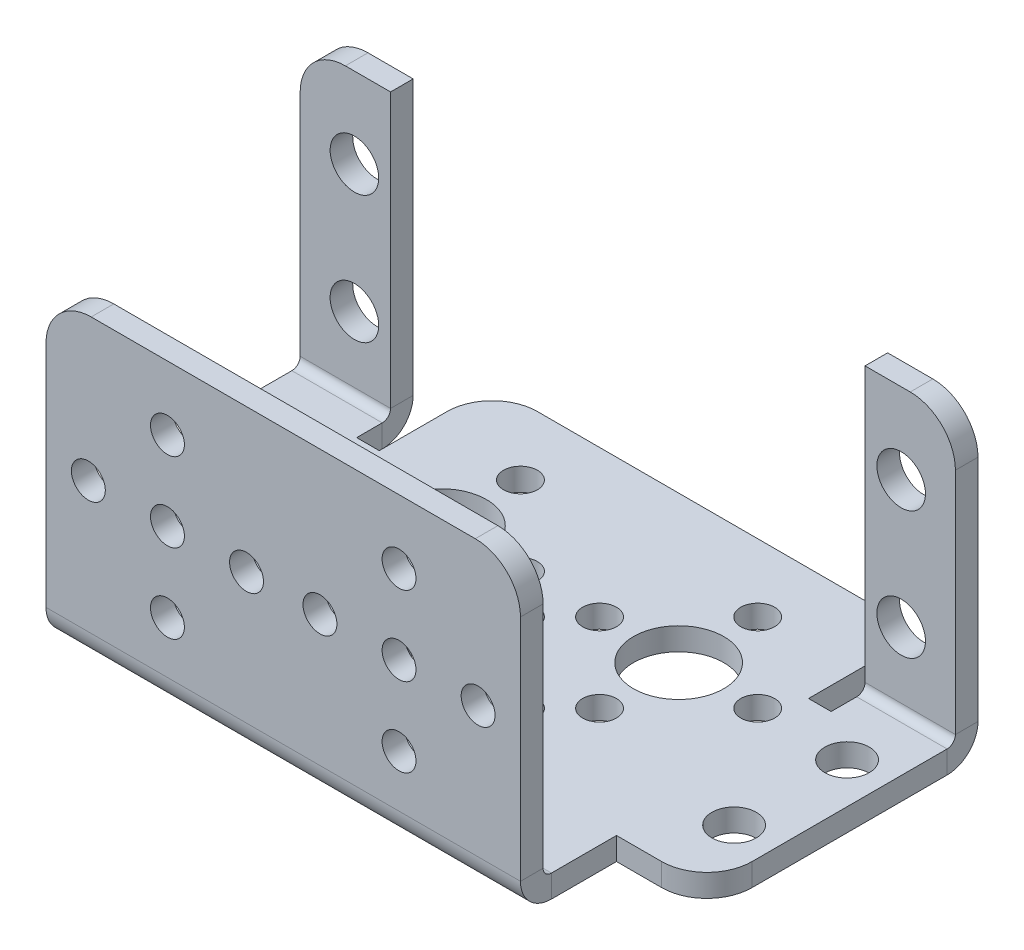
SolidWorks part; units mm, degrees
note: The reader was unsure of these and kept them because the rebuilt part matched: flange length of "Edge-Flange1", "Edge-Flange2", "Edge-Flange3".
ref_plane "Front Plane" through (0, 0, 0) normal (0, 0, 1) x (1, 0, 0)
ref_plane "Top Plane" through (0, 0, 0) normal (0, 1, 0) x (1, 0, 0)
ref_plane "Right Plane" through (0, 0, 0) normal (1, 0, 0) x (0, 0, -1)
sketch "Sketch2" plane through (0, 0, 0) normal (0, 1, 0) x (1, 0, 0)
  line L0 (-21, 12.8159) -> (-29, 12.8159)
  line L1 (-29, 12.8159) -> (-29, -9.1841)
  line L2 (-29, -9.1841) -> (-21, -9.1841)
  line L3 (-21, -9.1841) -> (-21, -15.6841)
  line L4 (-21, -15.6841) -> (21, -15.6841)
  line L5 (21, -15.6841) -> (21, -9.1841)
  line L6 (21, -9.1841) -> (29, -9.1841)
  line L7 (29, -9.1841) -> (29, 12.8159)
  line L8 (29, 12.8159) -> (21, 12.8159)
  line L9 (21, 12.8159) -> (21, 9.8159)
  line L10 (21, 9.8159) -> (19, 9.8159)
  line L11 (19, 9.8159) -> (19, 19.8159)
  line L12 (19, 19.8159) -> (-19, 19.8159)
  line L13 (-19, 19.8159) -> (-19, 9.8159)
  line L14 (-19, 9.8159) -> (-21, 9.8159)
  line L15 (-21, 9.8159) -> (-21, 12.8159)
  line L16 (-25, -3.1841) -> (-25, 6.8159) construction
  line L17 (25.4097, 6.8159) -> (25.4097, -3.1841) construction
  line L18 (-25, 6.8159) -> (-25, 12.8159) construction
  line L19 (-25, -3.1841) -> (-25, -9.1841) construction
  line L21 (-10.5, 6.8159) -> (10.5, 6.8159) construction
  circle A0 centre (-25, -3.1841) radius 1.9668
  circle A1 centre (-25, 6.8159) radius 1.9668
  circle A2 centre (25.4097, 6.8159) radius 1.9668
  circle A3 centre (25.4097, -3.1841) radius 1.9668
  circle A4 centre (-10.5, 6.8159) radius 4
  circle A5 centre (10.5, 6.8159) radius 4
  circle A6 centre (0, -3.6841) radius 4
  circle A7 centre (-10.5, 6.8159) radius 7 construction
  circle A8 centre (10.5, 6.8159) radius 7 construction
  circle A9 centre (0, -3.6841) radius 7 construction
  circle A10 centre (-10.5, 13.8159) radius 1.5
  circle A11 centre (10.5, 13.8159) radius 1.5
  circle A12 centre (0, -10.6841) radius 1.5
  circle A13 centre (-3.5, 6.8159) radius 1.5
  circle A14 centre (-10.5, -0.1841) radius 1.5
  circle A15 centre (-17.5, 6.8159) radius 1.5
  circle A16 centre (17.5, 6.8159) radius 1.5
  circle A17 centre (10.5, -0.1841) radius 1.5
  circle A18 centre (3.5, 6.8159) radius 1.5
  circle A19 centre (-7, -3.6841) radius 1.5
  circle A20 centre (0, 3.3159) radius 1.5
  circle A21 centre (7, -3.6841) radius 1.5
  point P2 (0, -15.6841)
  point P17 (0, 19.8159)
  point P19 (-25, 12.8159)
  point P28 (25.4097, 1.8159)
  point P29 (-25, 1.8159)
  point P36 (0, 6.8159)
  point P48 (-20, 9.8159)
  point P57 (-10.5, 6.8159)
  point P64 (10.5, 6.8159)
  point P71 (0, -3.6841)
  dimension "D8" = 8
  dimension "D10" = 14
  dimension "D11" = 3
  dimension "D1" = 58
  dimension "D2" = 35.5
  dimension "D3" = 28.5
  dimension "D4" = 38
  dimension "D5" = 12.5
  dimension "D6" = 10
  dimension "D7" = 21
  dimension "D9" = 12
  dimension "D15" = 2
  dimension "D16" = 10
  dimension "D12" = 4
  dimension "D13" = 4
  dimension "D14" = 4
base flange "Base-Flange1" sketch "Sketch2" thickness 2 reverse thickness direction no parameters "D1"=0.7366
fillet "Fillet1" radius 4 4 edges at (-19, -1, -19.8159) (19, -1, -19.8159) (29, -1, 9.1841) (-29, -1, 9.1841)
edge flange "Edge-Flange1" sketch "Sketch9" flange angle 90 flange length 27 flange position material outside bend radius 0.7366 thickness 2 relief rectangular parameters "D6"=10
sketch "Sketch9" plane through (0, 0, -12.8159) normal (0, 0, -1) x (-1, 0, 0)
  line L2 (21, 0) -> (21, 25)
  line L3 (21, 25) -> (29, 25)
  line L4 (29, 25) -> (29, 0)
  line L7 (21, 0) -> (29, 0) construction
  line L8 (21, 0) -> (29, 0)
bend "EdgeBend1" bend radius 0.7366 bend angle 90 parameters "D5"=1
edge flange "Edge-Flange2" sketch "Sketch12" flange angle 90 flange length 27 flange position material outside bend radius 0.7366 thickness 2 relief rectangular parameters "D6"=10
sketch "Sketch12" plane through (0, 0, -12.8159) normal (0, 0, -1) x (-1, 0, 0)
  line L0 (-29, 0) -> (-21, 0) construction
  line L1 (-29, 0) -> (-21, 0)
  line L2 (-29, 0) -> (-29, 25)
  line L3 (-29, 25) -> (-21, 25)
  line L4 (-21, 25) -> (-21, 0)
bend "EdgeBend2" bend radius 0.7366 bend angle 90 parameters "D5"=2
edge flange "Edge-Flange3" sketch "Sketch15" flange angle 90 flange length 27 flange position material outside bend radius 0.7366 thickness 2 relief rectangular parameters "D6"=10
sketch "Sketch15" plane through (0, 0, 15.6841) normal (0, 0, 1) x (1, 0, 0)
  line L0 (-21, 0) -> (21, 0) construction
  line L1 (-21, 0) -> (21, 0)
  line L2 (-21, 0) -> (-21, 25)
  line L3 (-21, 25) -> (21, 25)
  line L4 (21, 25) -> (21, 0)
bend "EdgeBend3" bend radius 0.7366 bend angle 90 parameters "D5"=3
fillet "Fillet2" radius 4 2 edges at (29, 25, -13.8159) (-29, 25, -13.8159)
fillet "Fillet3" radius 4 2 edges at (21, 25, 16.6841) (-21, 25, 16.6841)
sketch "Sketch16" plane through (0, 0, 17.6841) normal (0, 0, 1) x (1, 0, 0)
  line L0 (-10.25, 12.331) -> (10.25, 12.331) construction
  line L1 (-24.2, 17.8706) -> (24.2, 17.8706) construction
  line L2 (-24.2, 17.8706) -> (-24.2, 6.5706) construction
  line L3 (-24.2, 6.5706) -> (24.2, 6.5706) construction
  line L4 (24.2, 17.8706) -> (24.2, 6.5706) construction
  circle A0 centre (-24.2, 17.8706) radius 2.15
  circle A1 centre (24.2, 17.8706) radius 2.15
  circle A2 centre (-24.2, 6.5706) radius 2.15
  circle A3 centre (24.2, 6.5706) radius 2.15
  circle A4 centre (-10.25, 12.331) radius 7 construction
  circle A5 centre (10.25, 12.331) radius 7 construction
  circle A6 centre (-10.25, 12.331) radius 1.5
  circle A7 centre (-10.25, 5.331) radius 1.5
  circle A9 centre (10.25, 12.331) radius 1.5
  circle A10 centre (10.25, 5.331) radius 1.5
  circle A11 centre (-17.25, 12.331) radius 1.5
  circle A12 centre (-10.25, 19.331) radius 1.5
  circle A13 centre (-3.25, 12.331) radius 1.5
  circle A14 centre (3.25, 12.331) radius 1.5
  circle A15 centre (10.25, 19.331) radius 1.5
  circle A16 centre (17.25, 12.331) radius 1.5
  point P12 (0, 6.5706)
  point P16 (0, 12.331)
  point P38 (-10.25, 12.331)
  point P44 (10.25, 12.331)
  dimension "D3" = 4.3
  dimension "D4" = 14
  dimension "D5" = 3
  dimension "D1" = 48.4
  dimension "D2" = 11.3
  dimension "D8" = 13.95
  dimension "D6" = 4
  dimension "D7" = 4
extrude "Cut-Extrude1" cut sketch "Sketch16" against normal through all normal cut yes
sketch "Bend-Lines1" [suppressed] plane through (0, 0, 0) normal (0, 1, 0) x (1, 0, 0)
sketch "Bounding-Box1" [suppressed] plane through (0, 0, 0) normal (0, 1, 0) x (1, 0, 0)
sheet metal parameters "Sheet-Metal1" thickness 2 parameters "D1"=0.7366
flat pattern "Flat-Pattern1" [suppressed]
sketch "Bend-Lines2" plane through (0, 0, 0) normal (0, 1, 0) x (1, 0, 0)
sketch3d "Bounding-Box2" [suppressed]
  line L0 (-29, -15.6841, 0) -> (29, -15.6841, 0) construction
  line L1 (-29, 19.8159, 0) -> (29, 19.8158, 0) construction
  line L2 (-29, -15.6841, 0) -> (-29, 19.8159, 0) construction
  line L3 (29, -15.6841, 0) -> (29, 19.8158, 0) construction
sheet metal parameters "Sheet-Metal2" thickness 2 parameters "D1"=0.7366
flat pattern "Flat-Pattern1"
sketch "Bend-Lines2" plane through (0, 0, 0) normal (0, 1, 0) x (1, 0, 0)
  line L0 (-21, 13.4432) -> (-29, 13.4432) construction
  line L1 (-21, 13.4432) -> (-29, 13.4432) construction
sketch3d "Bounding-Box2" [suppressed]
  line L0 (-29, -15.6841, 0) -> (29, -15.6841, 0) construction
  line L1 (-29, 39.0705, 0) -> (29, 39.0705, 0) construction
  line L2 (-29, -15.6841, 0) -> (-29, 39.0705, 0) construction
  line L3 (29, -15.6841, 0) -> (29, 39.0705, 0) construction
bend of the flat pattern "Flatten-<EdgeBend1>1"
sheet metal parameters "Sheet-Metal3" thickness 2 parameters "D1"=0.7366
flat pattern "Flat-Pattern1"
sketch "Bend-Lines2" plane through (0, 0, 0) normal (0, 1, 0) x (1, 0, 0)
  line L0 (-21, 13.4432) -> (-29, 13.4432) construction
  line L1 (-21, 13.4432) -> (-29, 13.4432) construction
  line L2 (29, 13.4432) -> (21, 13.4432) construction
  line L3 (29, 13.4432) -> (21, 13.4432) construction
sketch3d "Bounding-Box2" [suppressed]
  line L0 (-29, -15.6841, 0) -> (29, -15.6841, 0) construction
  line L1 (-29, 39.0705, 0) -> (29, 39.0705, 0) construction
  line L2 (-29, -15.6841, 0) -> (-29, 39.0705, 0) construction
  line L3 (29, -15.6841, 0) -> (29, 39.0705, 0) construction
bend of the flat pattern "Flatten-<EdgeBend1>1"
bend of the flat pattern "Flatten-<EdgeBend2>1"
sheet metal parameters "Sheet-Metal4" thickness 2 parameters "D1"=0.7366
flat pattern "Flat-Pattern1"
sketch "Bend-Lines2" plane through (0, 0, 0) normal (0, 1, 0) x (1, 0, 0)
  line L0 (-21, 13.4432) -> (-29, 13.4432) construction
  line L1 (-21, 13.4432) -> (-29, 13.4432) construction
  line L2 (29, 13.4432) -> (21, 13.4432) construction
  line L3 (29, 13.4432) -> (21, 13.4432) construction
  line L4 (-21, -16.3115) -> (21, -16.3115) construction
  line L5 (-21, -16.3115) -> (21, -16.3115) construction
sketch3d "Bounding-Box2" [suppressed]
  line L0 (29, 39.0705, 0) -> (29, -41.9388, 0) construction
  line L1 (-29, 39.0705, 0) -> (-29, -41.9388, 0) construction
  line L2 (29, 39.0705, 0) -> (-29, 39.0705, 0) construction
  line L3 (29, -41.9388, 0) -> (-29, -41.9388, 0) construction
bend of the flat pattern "Flatten-<EdgeBend1>1"
bend of the flat pattern "Flatten-<EdgeBend2>1"
bend of the flat pattern "Flatten-<EdgeBend3>1"
sheet metal parameters "Sheet-Metal5" thickness 2 parameters "D1"=0.7366
flat pattern "Flat-Pattern1"
sketch "Bend-Lines2" plane through (0, 0, 0) normal (0, 1, 0) x (1, 0, 0)
  line L0 (-21, 13.4432) -> (-29, 13.4432) construction
  line L1 (-21, 13.4432) -> (-29, 13.4432) construction
  line L2 (29, 13.4432) -> (21, 13.4432) construction
  line L3 (29, 13.4432) -> (21, 13.4432) construction
  line L4 (-21, -16.3115) -> (21, -16.3115) construction
  line L5 (-21, -16.3115) -> (21, -16.3115) construction
sketch3d "Bounding-Box2" [suppressed]
  line L0 (29, 39.0705, 0) -> (29, -41.9388, 0) construction
  line L1 (-29, 39.0705, 0) -> (-29, -41.9388, 0) construction
  line L2 (29, 39.0705, 0) -> (-29, 39.0705, 0) construction
  line L3 (29, -41.9388, 0) -> (-29, -41.9388, 0) construction
bend of the flat pattern "Flatten-<EdgeBend1>1"
bend of the flat pattern "Flatten-<EdgeBend2>1"
bend of the flat pattern "Flatten-<EdgeBend3>1"
